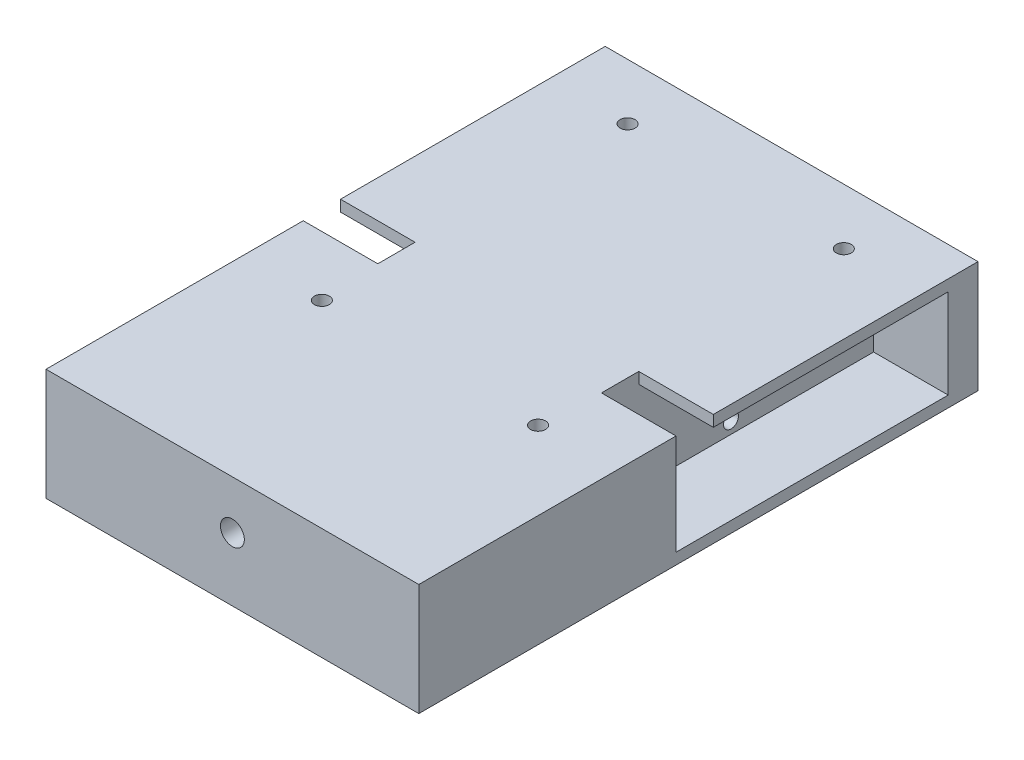
SolidWorks part; units mm, degrees
ref_plane "Front Plane" through (0, 0, 0) normal (0, 0, 1) x (1, 0, 0)
ref_plane "Top Plane" through (0, 0, 0) normal (0, 1, 0) x (1, 0, 0)
ref_plane "Right Plane" through (0, 0, 0) normal (1, 0, 0) x (0, 0, -1)
sketch "Sketch1" plane through (0, 0, 0) normal (0, 1, 0) x (1, 0, 0)
  line L1 (-50, 75) -> (50, 75)
  line L2 (-50, 75) -> (-50, -75)
  line L3 (-50, -75) -> (50, -75)
  line L4 (50, 75) -> (50, -75)
  line L5 (-50, 75) -> (50, -75) construction
  line L6 (-50, -75) -> (50, 75) construction
  point P0 (0, 0)
  dimension "D1" = 100
  dimension "D2" = 150
extrude "box" add sketch "Sketch1" against normal blind 30
sketch "Sketch2" plane through (50, 0, 0) normal (1, 0, 0) x (0, 0, -1)
  line L0 (0, 0) -> (0, -30) construction
  line L1 (-75, -30) -> (75, -30) construction
  line L2 (-75, -15) -> (75, -15) construction
  line L3 (-75, -30) -> (-75, 0) construction
  line L4 (75, -30) -> (75, 0) construction
  line L6 (-6, -3) -> (67, -3)
  line L7 (-6, -3) -> (-6, -27)
  line L8 (-6, -27) -> (67, -27)
  line L9 (67, -3) -> (67, -27)
  line L10 (-6, -3) -> (67, -27) construction
  line L11 (-6, -27) -> (67, -3) construction
  point P11 (30.5, -15)
  dimension "D1" = 24
  dimension "D2" = 73
  dimension "D3" = 8
extrude "motor compartment" cut sketch "Sketch2" against normal blind 20
sketch "Sketch3" plane through (50, 0, 0) normal (1, 0, 0) x (0, 0, -1)
  line L0 (-75, 0) -> (75, 0) construction
  line L1 (-6, -3) -> (4, -3)
  line L2 (-6, -3) -> (-6, 0)
  line L3 (-6, 0) -> (4, 0)
  line L4 (4, -3) -> (4, 0)
  dimension "D1" = 10
extrude "motor wire passthrough" cut sketch "Sketch3" against normal up to surface (20 mm away) up to face at (30, -15, -30.5)
sketch "Sketch4" plane through (30, 0, 0) normal (1, 0, 0) x (0, 0, -1)
  line L0 (67, -15) -> (-49933, -15) construction
  line L1 (67, -27) -> (67, -3) construction
  line L2 (67, -27) -> (67, -3) construction
  line L3 (67, -27) -> (67, -3) construction
  line L4 (28.75, -3) -> (28.75, -27) construction
  line L5 (67, -3) -> (4, -3) construction
  line L6 (-6, -27) -> (67, -27) construction
  circle A0 centre (63, -15) radius 1.75
  circle A1 centre (28.75, -6.25) radius 2
  circle A2 centre (28.75, -23.75) radius 2
  point P4 (67, -15)
  dimension "D1" = 3.5
  dimension "D4" = 4
  dimension "D2" = 4
  dimension "D3" = 34.25
  dimension "D5" = 8.75
extrude "motor screw mount" cut sketch "Sketch4" against normal blind 10
mirror "motor compartment mirror" about plane through (0, 0, 0) normal (1, 0, 0) of "motor screw mount", "motor compartment", "motor wire passthrough"
sketch "Sketch5" plane through (0, 0, 0) normal (0, 1, 0) x (1, 0, 0)
  line L0 (0, 75) -> (0, -75) construction
  line L1 (50, 75) -> (-50, 75) construction
  line L2 (-50, -75) -> (50, -75) construction
  line L3 (50, 60) -> (-50, 60) construction
  line L4 (50, 4) -> (50, 75) construction
  line L5 (-50, 75) -> (-50, 4) construction
  line L6 (50, -22) -> (-50, -22) construction
  line L7 (50, -75) -> (50, -6) construction
  line L8 (-50, -6) -> (-50, -75) construction
  circle A0 centre (-29, 60) radius 2
  circle A1 centre (-29, -22) radius 2
  circle A2 centre (29, 60) radius 2
  circle A3 centre (29, -22) radius 2
  dimension "D4" = 4
  dimension "D3" = 4
  dimension "D1" = 15
  dimension "D2" = 82
  dimension "D5" = 29
extrude "Maker Pi mount holes" cut sketch "Sketch5" against normal blind 8
sketch "Sketch6" plane through (0, -30, 0) normal (0, -1, 0) x (1, 0, 0)
  line L0 (0, 0) -> (0, 75) construction
  line L1 (-50, 75) -> (50, 75) construction
  line L2 (-50, 75) -> (50, 75) construction
  line L4 (-12, 65) -> (12, 65)
  line L5 (-12, 65) -> (-12, 37)
  line L6 (-12, 37) -> (12, 37)
  line L7 (12, 65) -> (12, 37)
  line L8 (-12, 65) -> (12, 37) construction
  line L9 (-12, 37) -> (12, 65) construction
  point P5 (0, 51)
  dimension "D1" = 24
  dimension "D2" = 28
  dimension "D3" = 10
extrude "caster mount" cut sketch "Sketch6" against normal blind 1
sketch "Sketch7" plane through (0, 0, 75) normal (0, 0, 1) x (1, 0, 0)
  line L0 (0, 0) -> (0, -30) construction
  line L1 (-50, -30) -> (50, -30) construction
  circle A0 centre (0, -13) radius 3.2
  dimension "D1" = 6.4
  dimension "D2" = 13
extrude "front mount hole" cut sketch "Sketch7" against normal blind 25.4
mirror "back mount hole" about plane through (0, 0, 0) normal (0, 0, 1) of "front mount hole"
equation "\"D5@Sketch4\"=17.5mm/2"
equation "\"D4@Sketch5\"=\"D3@Sketch5\""
equation "\"D5@Sketch5\"=58mm/2"
